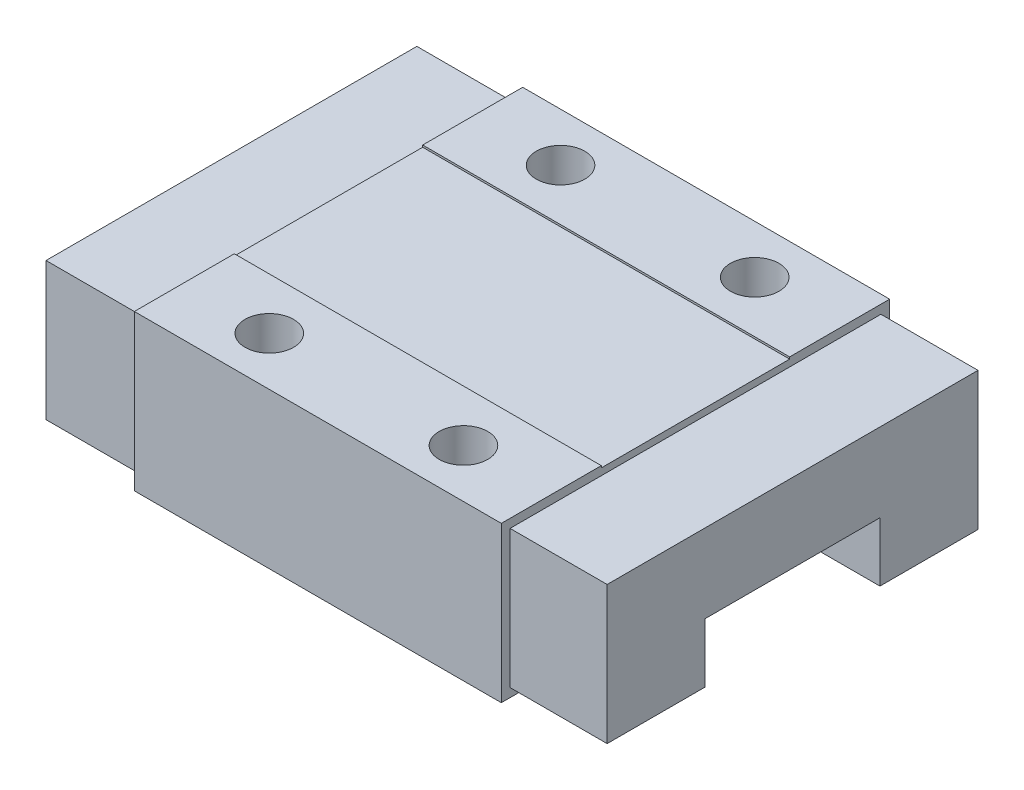
SolidWorks part; units mm, degrees
ref_plane "前视基准面" through (0, 0, 0) normal (0, 0, 1) x (1, 0, 0)
ref_plane "上视基准面" through (0, 0, 0) normal (0, 1, 0) x (1, 0, 0)
ref_plane "右视基准面" through (0, 0, 0) normal (1, 0, 0) x (0, 0, -1)
sketch "草图1" plane through (0, 0, 0) normal (1, 0, 0) x (0, 0, -1)
  line L1 (-10, 4) -> (10, 4)
  line L2 (-10, 4) -> (-10, -4)
  line L3 (-10, -4) -> (10, -4)
  line L4 (10, 4) -> (10, -4)
  line L5 (-10, 4) -> (10, -4) construction
  line L6 (-10, -4) -> (10, 4) construction
  point P0 (0, 0)
  dimension "D1" = 8
  dimension "D2" = 20
extrude "凸台-拉伸1" add sketch "草图1" along normal mid plane 18.9
sketch "草图2" plane through (0, 0, 0) normal (1, 0, 0) x (0, 0, -1)
  line L0 (10, 4) -> (-10, 4) construction
  line L1 (-4.85, 4.1) -> (4.85, 4.1)
  line L2 (-4.85, 4.1) -> (-4.85, 3.9)
  line L3 (-4.85, 3.9) -> (4.85, 3.9)
  line L4 (4.85, 4.1) -> (4.85, 3.9)
  line L5 (-4.85, 4.1) -> (4.85, 3.9) construction
  line L6 (-4.85, 3.9) -> (4.85, 4.1) construction
  point P0 (0, 4)
  dimension "D1" = 0.2
  dimension "D2" = 9.7
extrude "切除-拉伸1" cut sketch "草图2" against normal mid plane 20
sketch "草图3" plane through (0, 0, 0) normal (1, 0, 0) x (0, 0, -1)
  line L1 (-9.55, 3.55) -> (9.55, 3.55)
  line L2 (-9.55, 3.55) -> (-9.55, -3.55)
  line L3 (-9.55, -3.55) -> (9.55, -3.55)
  line L4 (9.55, 3.55) -> (9.55, -3.55)
  line L5 (-9.55, 3.55) -> (9.55, -3.55) construction
  line L6 (-9.55, -3.55) -> (9.55, 3.55) construction
  point P0 (0, 0)
  dimension "D1" = 7.1
  dimension "D2" = 19.1
extrude "凸台-拉伸2" add sketch "草图3" along normal mid plane 28.9
sketch "草图4" plane through (0, 0, 0) normal (1, 0, 0) x (0, 0, -1)
  line L0 (-10, -4) -> (10, -4) construction
  line L1 (-4.5, -4) -> (4.5, -4)
  line L2 (-4.5, -4) -> (-4.5, -0.5)
  line L3 (-4.5, -0.5) -> (4.5, -0.5)
  line L4 (4.5, -4) -> (4.5, -0.5)
  dimension "D1" = 3.5
  dimension "D2" = 9
  dimension "D3" = 4.5
extrude "切除-拉伸2" cut sketch "草图4" against normal mid plane 30
sketch "草图5" plane through (0, 4, 0) normal (0, 1, 0) x (1, 0, 0)
  line L1 (-5, 7.5) -> (5, 7.5) construction
  line L2 (-5, 7.5) -> (-5, -7.5) construction
  line L3 (-5, -7.5) -> (5, -7.5) construction
  line L4 (5, 7.5) -> (5, -7.5) construction
  line L5 (-5, 7.5) -> (5, -7.5) construction
  line L6 (-5, -7.5) -> (5, 7.5) construction
  circle A0 centre (-5, 7.5) radius 1.25
  circle A1 centre (5, 7.5) radius 1.25
  circle A2 centre (5, -7.5) radius 1.25
  circle A3 centre (-5, -7.5) radius 1.25
  point P0 (0, 0)
  dimension "D3" = 2.5
  dimension "D4" = 2.5
  dimension "D5" = 2.5
  dimension "D6" = 2.5
  dimension "D1" = 15
  dimension "D2" = 10
extrude "切除-拉伸3" cut sketch "草图5" against normal blind 3
cosmetic thread "装饰螺纹线1" parameters "D2"=3
cosmetic thread "装饰螺纹线2" parameters "D2"=3
cosmetic thread "装饰螺纹线3" parameters "D2"=3
cosmetic thread "装饰螺纹线4" parameters "D2"=3
